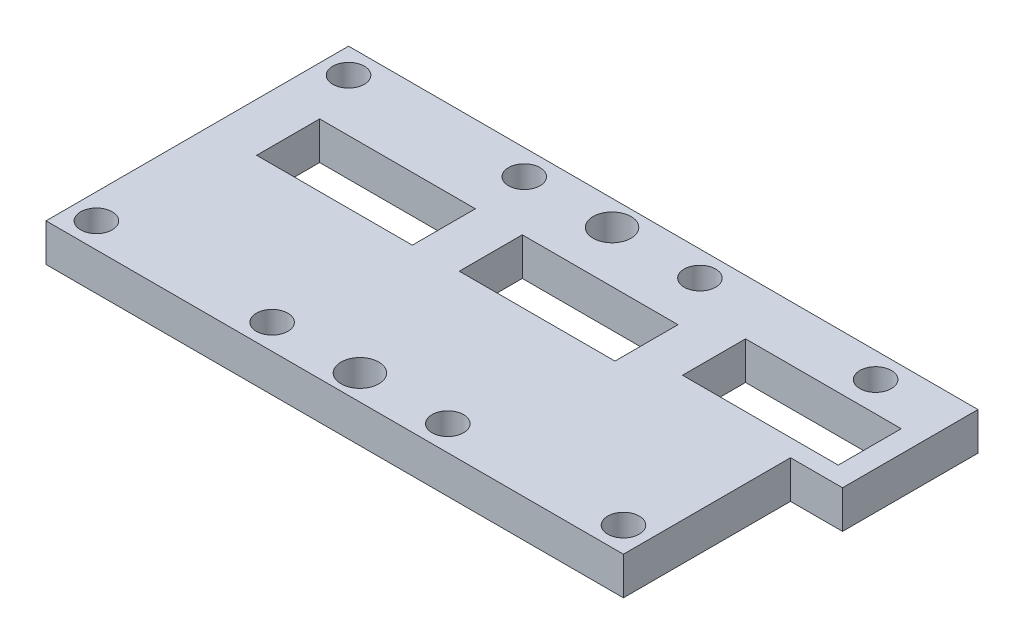
SolidWorks part; units mm, degrees
material "Plain Carbon Steel"
ref_plane "Front Plane" through (0, 0, 0) normal (0, 0, 1) x (1, 0, 0)
ref_plane "Top Plane" through (0, 0, 0) normal (0, 1, 0) x (1, 0, 0)
ref_plane "Right Plane" through (0, 0, 0) normal (1, 0, 0) x (0, 0, -1)
sketch "Sketch1" plane through (0, 0, 0) normal (0, 1, 0) x (1, 0, 0)
  line L0 (-229, 15.28) -> (-229, 9.28) construction
  line L1 (-229, -60) -> (0, -60)
  line L2 (-229, -60) -> (-229, 60)
  line L3 (-229, 60) -> (0, 60)
  line L4 (0, -60) -> (0, 60)
  point P0 (0, 0)
  dimension "D1" = 120
  dimension "D2" = 229
extrude "Boss-Extrude1" add sketch "Sketch1" against normal blind 15
sketch "Sketch2" plane through (0, 0, 0) normal (0, 1, 0) x (1, 0, 0)
  line L0 (21.6325, 5.27) -> (21.6325, 60) construction
  line L1 (0, 60) -> (20.6325, 60)
  line L2 (0, 60) -> (0, 6.27)
  line L3 (0, 6.27) -> (20.6325, 6.27)
  line L4 (20.6325, 60) -> (20.6325, 6.27)
  line L5 (1, 5.27) -> (21.6325, 5.27) construction
  dimension "D1" = 1
  dimension "D2" = 1
extrude "Boss-Extrude2" add sketch "Sketch2" against normal up to surface (15 mm away) up to face at (-114.5, -15, 0)
sketch "Sketch3" plane through (0, 0, 0) normal (0, 1, 0) x (1, 0, 0)
  line L0 (-48.75, 9.28) -> (-48.75, 26.191) construction
  line L1 (-49.75, 13.191) -> (12, 13.191)
  line L2 (-49.75, 13.191) -> (-49.75, 38.191)
  line L3 (-49.75, 38.191) -> (12, 38.191)
  line L4 (12, 13.191) -> (12, 38.191)
  line L5 (11, 27.5) -> (11, 9.28) construction
  line L7 (-29.25, 28.191) -> (-48.75, 28.191) construction
  dimension "D1" = 1
  dimension "D2" = 1
  dimension "D3" = 25
  dimension "D4" = 10
extrude "Cut-Extrude1" cut sketch "Sketch3" against normal up to next
sketch "Sketch4" plane through (0, 0, 0) normal (0, 1, 0) x (1, 0, 0)
  line L0 (-69, 15.28) -> (-69, 9.28) construction
  line L1 (-129.75, 29.6524) -> (-68, 29.6524)
  line L2 (-129.75, 29.6524) -> (-129.75, 4.6524)
  line L3 (-129.75, 4.6524) -> (-68, 4.6524)
  line L4 (-68, 29.6524) -> (-68, 4.6524)
  line L5 (-128.75, 9.28) -> (-128.75, 15.28) construction
  line L6 (-109.25, 19.6524) -> (-128.75, 19.6524) construction
  dimension "D1" = 1
  dimension "D2" = 1
  dimension "D3" = 10
  dimension "D4" = 25
extrude "Cut-Extrude2" cut sketch "Sketch4" against normal up to next
sketch "Sketch5" plane through (0, 0, 0) normal (0, 1, 0) x (1, 0, 0)
  line L0 (-208.75, 9.28) -> (-208.75, 15.28) construction
  line L1 (-209.75, 29.28) -> (-148, 29.28)
  line L2 (-209.75, 29.28) -> (-209.75, 4.28)
  line L3 (-209.75, 4.28) -> (-148, 4.28)
  line L4 (-148, 29.28) -> (-148, 4.28)
  line L5 (-149, 15.28) -> (-149, 9.28) construction
  line L6 (-149, 19.28) -> (-168.75, 19.28) construction
  dimension "D1" = 1
  dimension "D2" = 1
  dimension "D3" = 10
  dimension "D4" = 25
extrude "Cut-Extrude3" cut sketch "Sketch5" against normal up to next
sketch "Sketch7" plane through (0, 0, 0) normal (0, 1, 0) x (1, 0, 0)
  circle A0 centre (-114.5, 50) radius 7.5 construction
  circle A1 centre (-114.5, -50) radius 7.5 construction
  circle A2 centre (-114.5, 50) radius 7.5
  circle A3 centre (-114.5, -50) radius 7.5
extrude "Cut-Extrude5" cut sketch "Sketch7" against normal up to next
sketch "Sketch14" plane through (0, 0, 0) normal (0, 1, 0) x (1, 0, 0)
  circle A0 centre (-219, -50) radius 6.25 construction
  circle A1 centre (-149.323, -50) radius 6.25 construction
  circle A2 centre (-79.646, -50) radius 6.25 construction
  circle A3 centre (-219, 50) radius 6.25 construction
  circle A7 centre (-219, 50) radius 6.25
  circle A8 centre (-9.969, -50) radius 6.25 construction
  circle A9 centre (-9.969, 50) radius 6.25 construction
  circle A10 centre (-79.646, 50) radius 6.25 construction
  circle A11 centre (-149.323, 50) radius 6.25 construction
  circle A12 centre (-219, -50) radius 6.25
  circle A13 centre (-149.323, -50) radius 6.25
  circle A14 centre (-79.646, -50) radius 6.25
  circle A15 centre (-9.969, -50) radius 6.25
  circle A16 centre (-9.969, 50) radius 6.25
  circle A17 centre (-79.646, 50) radius 6.25
  circle A18 centre (-149.323, 50) radius 6.25
extrude "Cut-Extrude7" cut sketch "Sketch14" against normal up to next
